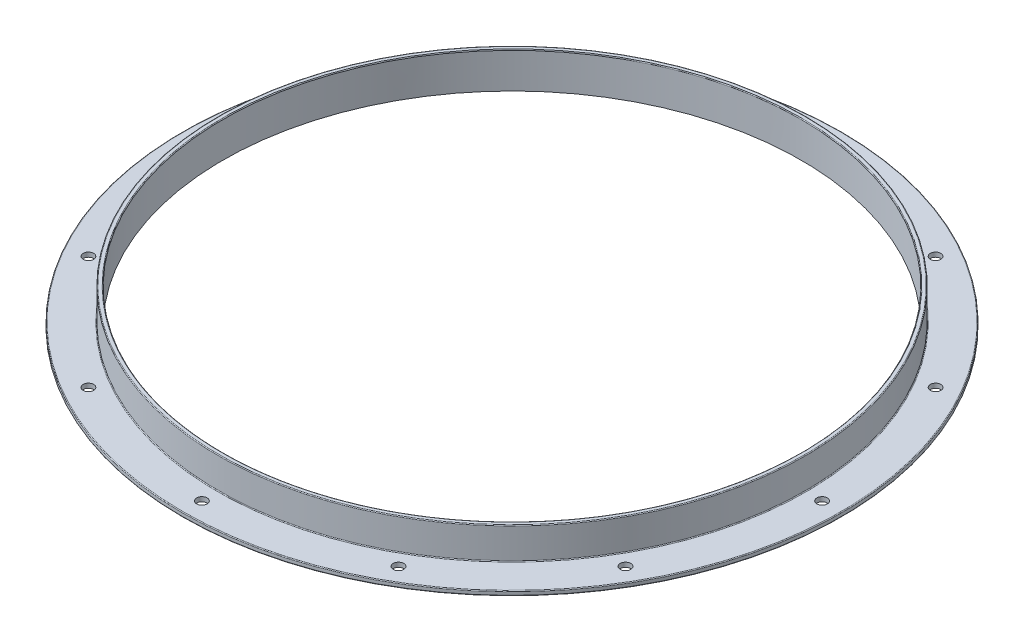
SolidWorks part; units mm, degrees
ref_plane "Front Plane" through (0, 0, 0) normal (0, 0, 1) x (1, 0, 0)
ref_plane "Top Plane" through (0, 0, 0) normal (0, 1, 0) x (1, 0, 0)
ref_plane "Right Plane" through (0, 0, 0) normal (1, 0, 0) x (0, 0, -1)
sketch "Sketch1" plane through (0, 0, 0) normal (1, 0, 0) x (0, 0, -1)
  line L0 (306.3875, 0) -> (349.25, 0)
  line L1 (349.25, 0) -> (349.25, 4.7625)
  line L2 (349.25, 4.7625) -> (311.15, 4.7625)
  line L3 (311.15, 4.7625) -> (311.15, 38.1)
  line L4 (311.15, 38.1) -> (306.3875, 38.1)
  line L5 (0, 38.1) -> (0, 0) construction
  line L6 (0, 50.5185) -> (0, -6.35) construction
  line L7 (306.3875, 38.1) -> (306.3875, 0)
  dimension "Flange Thk" = 4.7625
  dimension "Depth" = 38.1
  dimension "Flange Ht" = 38.1
  dimension "D1" = 4.7625
  dimension "D2" = 6.35
  dimension "ID" = 612.775
revolve "Revolve1" add sketch "Sketch1" angle 360 about L5
sketch "Sketch2" plane through (0, 38.1, 0) normal (0, 1, 0) x (1, 0, 0)
  line L0 (12.7, 0) -> (311.15, 0) construction
  circle A0 centre (0, 0) radius 115.8875
  circle A2 centre (0, 0) radius 349.25 construction
  circle A4 centre (0, 0) radius 311.15 construction
  dimension "D1" = 298.45
  dimension "ID" = 231.775
fillet "Fillet3" radius 0.7938 2 edges at (0, 0, 349.25) (0, 4.7625, 349.25)
fillet "Fillet4" radius 0.7938 3 edges at (0, 38.1, 311.15) (0, 4.7625, 311.15) (0, 38.1, 306.3875)
sketch "Sketch3" plane through (0, 4.7625, 0) normal (0, 1, 0) x (-1, 0, 0)
  circle A0 centre (0, -328.6125) radius 5.5563
  circle A1 centre (0, 0) radius 328.6125 construction
  dimension "mounting hole size" = 11.1125
  dimension "BoltCircle" = 657.225
extrude "Cut-Extrude1" cut sketch "Sketch3" against normal through all
pattern_circular "CirPattern1" count 12 over 360 about axis through (0, 38.1, 0) along (0, 1, 0) of "Cut-Extrude1"
equation "\"D1@Fillet3\" = \"Flange Thk@Sketch1\"/6"
equation "\"D1@Fillet4\" = \"Flange Thk@Sketch1\"/6"
equation "\"D1@Sketch1\" = \"Flange Thk@Sketch1\""
